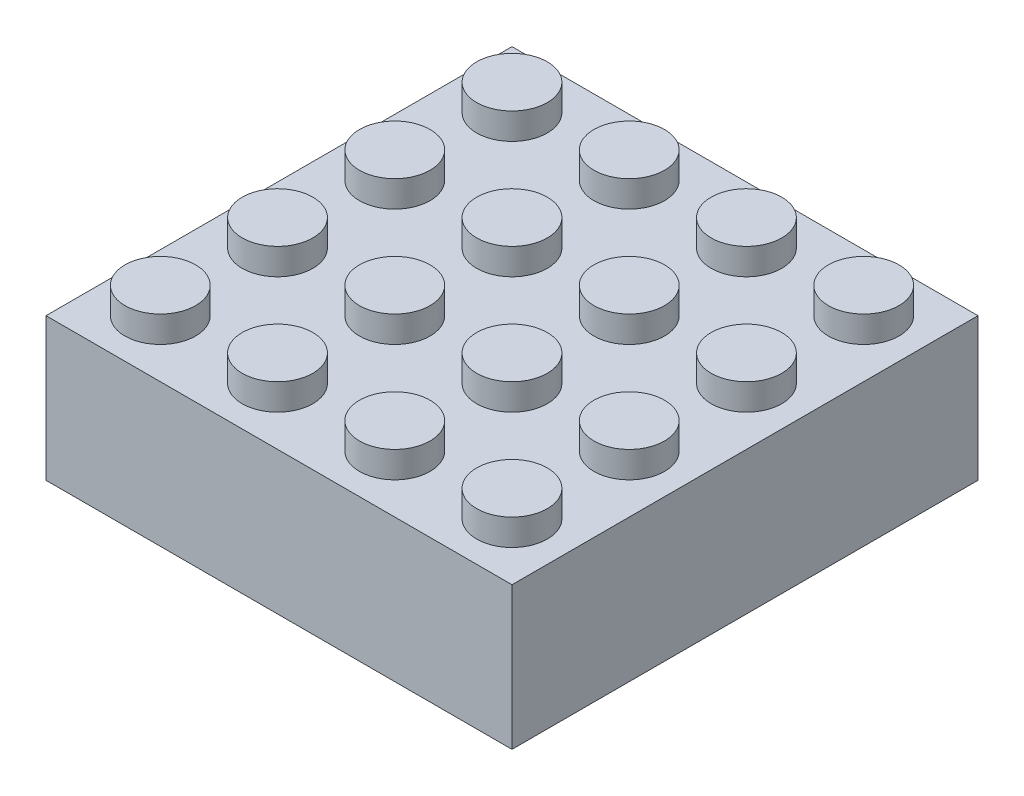
SolidWorks part; units mm, degrees
ref_plane "Front Plane" through (0, 0, 0) normal (0, 0, 1) x (1, 0, 0)
ref_plane "Top Plane" through (0, 0, 0) normal (0, 1, 0) x (1, 0, 0)
ref_plane "Right Plane" through (0, 0, 0) normal (1, 0, 0) x (0, 0, -1)
sketch "Sketch1" plane through (0, 0, 0) normal (0, 1, 0) x (1, 0, 0)
  line L1 (0, 0) -> (31.8, 0)
  line L2 (0, 0) -> (0, 31.8)
  line L3 (0, 31.8) -> (31.8, 31.8)
  line L4 (31.8, 0) -> (31.8, 31.8)
  dimension "D1" = 31.8
  dimension "D2" = 31.8
sketch "Sketch2" plane through (0, 0, 0) normal (0, 1, 0) x (1, 0, 0)
  line L0 (0, 0) -> (0, 31.8) construction
  line L1 (0, 31.8) -> (31.8, 31.8) construction
  circle A0 centre (3.9, 27.9) radius 2.41
  circle A1 centre (11.9, 27.9) radius 2.41
  circle A2 centre (19.9, 27.9) radius 2.41
  circle A3 centre (27.9, 27.9) radius 2.41
  circle A4 centre (11.9, 19.9) radius 2.41
  circle A5 centre (19.9, 19.9) radius 2.41
  circle A6 centre (27.9, 19.9) radius 2.41
  circle A7 centre (11.9, 11.9) radius 2.41
  circle A8 centre (19.9, 11.9) radius 2.41
  circle A9 centre (27.9, 11.9) radius 2.41
  circle A10 centre (11.9, 3.9) radius 2.41
  circle A11 centre (19.9, 3.9) radius 2.41
  circle A12 centre (27.9, 3.9) radius 2.41
  circle A13 centre (3.9, 19.9) radius 2.41
  circle A14 centre (3.9, 11.9) radius 2.41
  circle A15 centre (3.9, 3.9) radius 2.41
  dimension "D3" = 4.82
  dimension "D1" = 3.9
  dimension "D2" = 3.9
  dimension "D4" = 4
  dimension "D5" = 4
extrude "Boss-Extrude1" add sketch "Sketch2" along normal blind 1.8
extrude "Boss-Extrude2" add sketch "Sketch1" against normal blind 9.73
sketch "Sketch4" plane through (0, -9.73, 0) normal (0, -1, 0) x (1, 0, 0)
  line L1 (25.9143, -15.9285) -> (20.9143, -7.2683)
  line L2 (20.9143, -7.2683) -> (10.9143, -7.2683)
  line L3 (10.9143, -7.2683) -> (5.9143, -15.9285)
  line L4 (5.9143, -15.9285) -> (10.9143, -24.5888)
  line L5 (10.9143, -24.5888) -> (20.9143, -24.5888)
  line L6 (20.9143, -24.5888) -> (25.9143, -15.9285)
  point P1 (0, 0)
  point P8 (0, 0)
  point P17 (0, 0)
  point P18 (0, 0)
  point P40 (15.9, -15.9)
extrude "Cut-Extrude1" cut sketch "Sketch4" against normal blind 6.63 contours L6 L1 L2 L3 L4 L5 region at (15.9143, -9.73, -15.9285)
sketch "Sketch9" plane through (0, -9.73, 0) normal (0, -1, 0) x (1, 0, 0)
  line L0 (20.9143, -7.2683) -> (10.9143, -7.2683) construction
  line L2 (11.9143, -7.2683) -> (19.9143, -7.2683)
  line L3 (11.9143, -7.2683) -> (11.9143, -5.7683)
  line L4 (11.9143, -5.7683) -> (19.9143, -5.7683)
  line L5 (19.9143, -7.2683) -> (19.9143, -5.7683)
  dimension "D1" = 1
  dimension "D2" = 1
  dimension "D3" = 1.5
extrude "Boss-Extrude4" add sketch "Sketch9" along normal blind 1.5
sketch "Sketch10" plane through (19.9143, 0, 0) normal (1, 0, 0) x (0, 0, -1)
  line L0 (7.2683, -11.23) -> (7.8683, -10.23)
  line L1 (7.8683, -10.23) -> (7.2683, -9.73)
  line L2 (7.2683, -11.23) -> (7.2683, -9.73) construction
  line L3 (7.2683, -9.73) -> (7.2683, -11.23)
  dimension "D1" = 1
  dimension "D2" = 0.6
extrude "Boss-Extrude5" add sketch "Sketch10" against normal up to surface (8 mm away) up to face at (11.9143, -10.48, -6.5183)
sketch "Sketch11" plane through (19.9143, 0, 0) normal (1, 0, 0) x (0, 0, -1)
  line L0 (6.7683, -11.23) -> (5.7683, -9.73)
  line L1 (7.2683, -11.23) -> (5.7683, -11.23) construction
  line L2 (5.7683, -9.73) -> (5.7683, -11.23)
  line L3 (5.7683, -11.23) -> (6.7683, -11.23)
  dimension "D1" = 1
extrude "Cut-Extrude4" cut sketch "Sketch11" against normal up to next (8 mm away)
ref_axis "Axis2" through (15.9, 33.0797, -15.9) along (0, -1, 0)
pattern_circular "CirPattern3" count 6 over 360 about axis through (15.9, 33.0797, -15.9) along (0, -1, 0) of "Boss-Extrude4", "Boss-Extrude5", "Cut-Extrude4"
